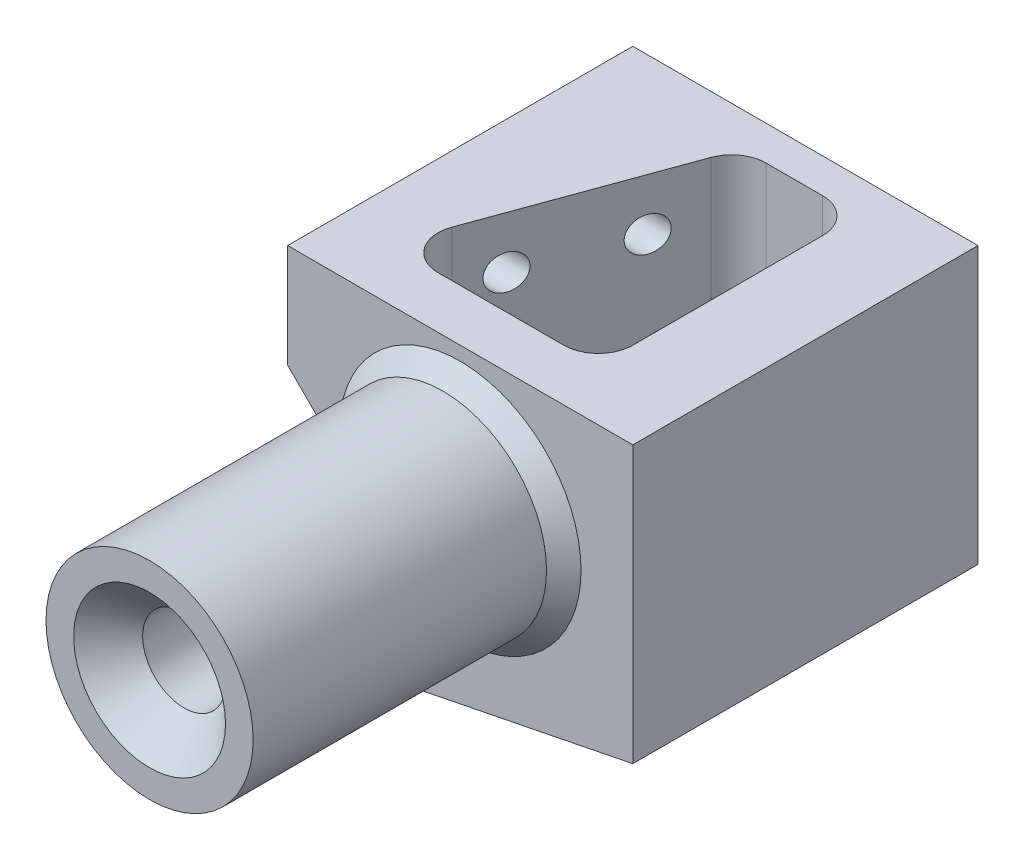
SolidWorks part; units mm, degrees
ref_plane "Front Plane" through (0, 0, 0) normal (0, 0, 1) x (1, 0, 0)
ref_plane "Top Plane" through (0, 0, 0) normal (0, 1, 0) x (1, 0, 0)
ref_plane "Right Plane" through (0, 0, 0) normal (1, 0, 0) x (0, 0, -1)
sketch "Sketch1" plane through (0, 0, 0) normal (0, 0, 1) x (1, 0, 0)
  line L0 (-4, -4.8) -> (5, -3)
  line L2 (-5, 2) -> (-5, 5)
  line L3 (-5, 5) -> (5, 5)
  line L4 (5, -3) -> (5, 5)
  line L5 (-5, -5) -> (5, 5) construction
  line L6 (-5, 5) -> (5, -5) construction
  line L7 (-4, 0.299) -> (5, 2.099) construction
  line L8 (-4, 5) -> (-4, -4.8)
  line L9 (-5, 2) -> (-4, 1)
  circle A0 centre (0, 1.099) radius 3
  point P0 (0, 0)
  point P15 (0, 0)
  point P16 (-5, 2.099)
  point P17 (-5, 0.1)
  point P18 (0, 0)
  point P19 (-4, 0.2988)
  dimension "D6" = 6
  dimension "D1" = 10
  dimension "D2" = 5
  dimension "D3" = 5
  dimension "D4" = 5
  dimension "D5" = 8
  dimension "D7" = 5
  dimension "D8" = 5
  dimension "D9" = 1
  dimension "D10" = 45
  dimension "D11" = 3
  dimension "D12" = 3.9223
extrude "Boss-Extrude1" add sketch "Sketch1" against normal blind 10 contours L3 L8 L0 L4 A0 | L2 L9 L8 L3 | A0 region at (-3.8669, -1.9, 0) region at (-4.4762, 3.2381, 0) region at (0, 1.099, 0)
extrude "Boss-Extrude2" add sketch "Sketch1<3>" along normal blind 9 contours A0 region at (0, 1.099, 0)
sketch "Sketch1<3>" plane through (0, 0, 0) normal (0, 0, 1) x (1, 0, 0) same geometry as "Sketch1"
sketch "Sketch2" plane through (-5, 0, 0) normal (-1, 0, 0) x (0, 0, 1)
  line L0 (-10, 5) -> (0, 5) construction
  line L1 (0, 2) -> (0, 5) construction
  circle A0 centre (-7, 3.5) radius 0.5
  circle A1 centre (-4, 3.5) radius 0.5
  point P6 (0, 0)
  point P7 (0, 0)
  dimension "D1" = 1
  dimension "D2" = 1
  dimension "D3" = 1.5
  dimension "D4" = 1.5
  dimension "D5" = 3
  dimension "D6" = 4
sketch "Sketch5" plane through (0, 5, 0) normal (0, 1, 0) x (1, 0, 0)
  line L0 (0, 10) -> (0, -8.9574) construction
  line L1 (-5, 10) -> (5, 10) construction
  line L2 (1.5, 9) -> (-0.1404, 9)
  line L3 (-5, 0) -> (5, 0) construction
  line L4 (2.5, 4) -> (2.5, 8)
  line L5 (0, 1.5) -> (1.5, 1.5)
  line L6 (2.5, 4) -> (2.5, 2.5)
  line L7 (0, 1.5) -> (-2.1422, 1.5)
  line L8 (-5, 7.5) -> (-5, 6.5) construction
  line L9 (-1.0801, 8.342) -> (-3.0819, 2.842)
  circle A0 centre (0, 4) radius 2.5 construction
  arc A1 (-0.1404, 9) -> (-1.0801, 8.342) centre (-0.1404, 8) ccw
  arc A2 (-3.0819, 2.842) -> (-2.1422, 1.5) centre (-2.1422, 2.5) ccw
  arc A3 (2.5, 2.5) -> (1.5, 1.5) centre (1.5, 2.5) cw
  arc A4 (2.5, 8) -> (1.5, 9) centre (1.5, 8) ccw
  dimension "D2" = 5
  dimension "D5" = 1
  dimension "D1" = 4
  dimension "D3" = 1
  dimension "D4" = 20
extrude "Cut-Extrude1" cut sketch "Sketch5" against normal blind 10
extrude "Cut-Extrude2" cut sketch "Sketch2" against normal blind 5
chamfer "Chamfer1" distance 0.5 angle 45 1 edges at (3, 1.099, 0)
hole_wizard "CSK for M2 Flat Head Machine Screw1" positions "Sketch6" profile "Sketch7" countersink size "M2" standard "ANSI Metric" end condition up to next
sketch "Sketch6" plane through (0, 0, 9) normal (0, 0, 1) x (1, 0, 0)
  point P0 (0, 1.099)
sketch "Sketch7" plane through (0, 1.099, 9) normal (1, 0, 0) x (0, -1, 0)
  line L0 (0, 0) -> (0, 10.5)
  line L1 (0, 10.5) -> (1.2, 10.5)
  line L2 (1.2, 10.5) -> (1.2, 1)
  line L3 (1.2, 1) -> (2.2, 0)
  line L5 (2.2, 0) -> (0, 0)
  line L6 (-1.2, 1) -> (-2.2, 0) construction
  line L11 (0, -6.35) -> (0, 107.95) construction
  dimension "Thru Hole Dia." = 2.4
  dimension "Thru Hole Depth" = 10.5
  dimension "Near C'Sink Dia." = 4.4
  dimension "Near C'Sink Angle" = 90
